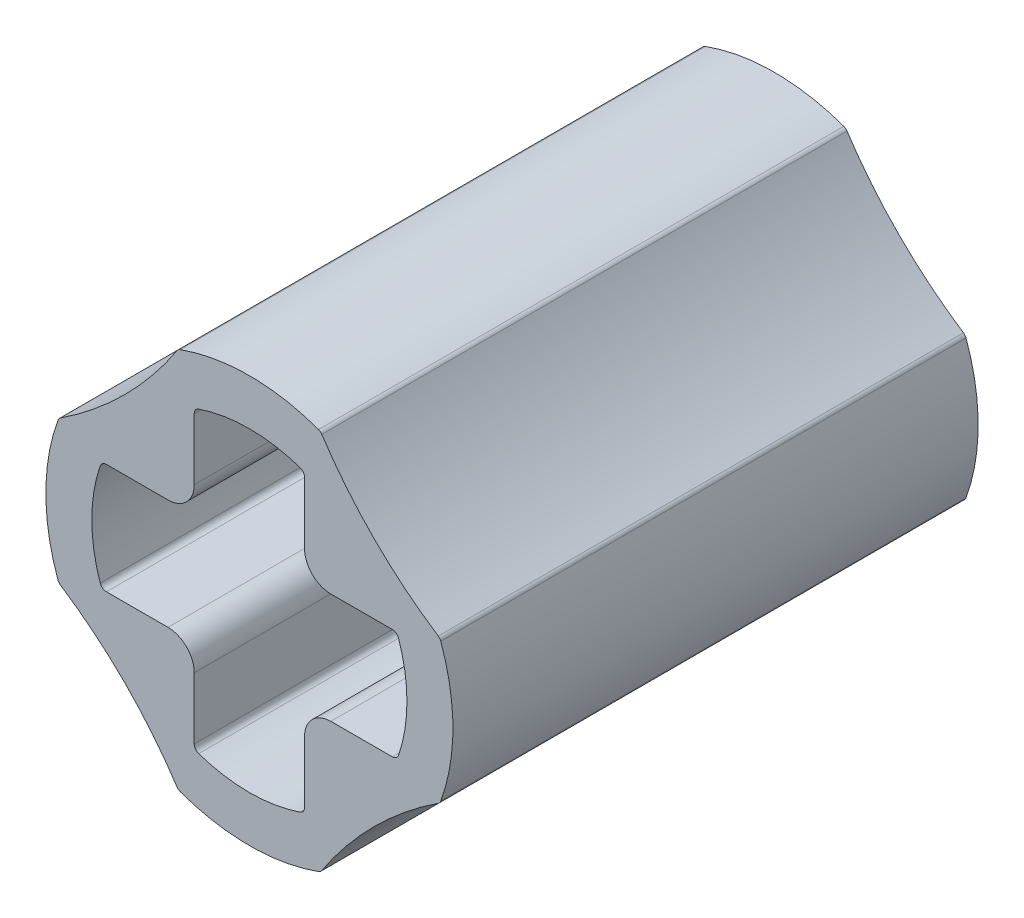
SolidWorks part; units mm, degrees
ref_plane "Front Plane" through (0, 0, 0) normal (0, 0, 1) x (1, 0, 0)
ref_plane "Top Plane" through (0, 0, 0) normal (0, 1, 0) x (1, 0, 0)
ref_plane "Right Plane" through (0, 0, 0) normal (1, 0, 0) x (0, 0, -1)
sketch "Sketch1" plane through (0, 0, 0) normal (0, 0, 1) x (1, 0, 0)
  line L0 (-1.085, -1.085) -> (-1.085, -2.9039)
  line L2 (-1.085, 2.9039) -> (-1.085, 1.085)
  line L4 (1.085, 2.9039) -> (1.085, 1.085)
  line L5 (-1.085, 2.9039) -> (1.085, -2.9039) construction
  line L6 (-1.085, -2.9039) -> (1.085, 2.9039) construction
  line L7 (-2.9039, 1.085) -> (-1.085, 1.085)
  line L9 (-2.9039, -1.085) -> (-1.085, -1.085)
  line L11 (-2.9039, 1.085) -> (2.9039, -1.085) construction
  line L12 (-2.9039, -1.085) -> (2.9039, 1.085) construction
  line L13 (1.085, -1.085) -> (1.085, -2.9039)
  line L14 (1.085, -1.085) -> (2.9039, -1.085)
  line L15 (1.085, 1.085) -> (2.9039, 1.085)
  arc A0 (1.085, 2.9039) -> (-1.085, 2.9039) centre (0, 0) ccw
  arc A1 (-2.9039, 1.085) -> (-2.9039, -1.085) centre (0, 0) ccw
  arc A2 (-1.085, -2.9039) -> (1.085, -2.9039) centre (0, 0) ccw
  arc A3 (2.9039, -1.085) -> (2.9039, 1.085) centre (0, 0) ccw
  dimension "D1" = 6.2
  dimension "D2" = 2.17
  dimension "D3" = 2.17
extrude "Boss-Extrude1" add sketch "Sketch1" along normal blind 8
sketch "Sketch2" plane through (0, 0, 0) normal (0, 0, 1) x (1, 0, 0)
  line L0 (0.84, -0.84) -> (2.2482, -0.84)
  line L2 (-0.84, 2.2482) -> (-0.84, 0.84)
  line L4 (0.84, 2.2482) -> (0.84, 0.84)
  line L5 (-0.84, 2.2482) -> (0.84, -2.2482) construction
  line L6 (-0.84, -2.2482) -> (0.84, 2.2482) construction
  line L7 (-2.2482, 0.84) -> (-0.84, 0.84)
  line L9 (-2.2482, -0.84) -> (-0.84, -0.84)
  line L11 (-2.2482, 0.84) -> (2.2482, -0.84) construction
  line L12 (-2.2482, -0.84) -> (2.2482, 0.84) construction
  line L13 (-0.84, -0.84) -> (-0.84, -2.2482)
  line L14 (0.84, 0.84) -> (2.2482, 0.84)
  line L15 (0.84, -0.84) -> (0.84, -2.2482)
  arc A0 (-2.2482, 0.84) -> (-2.2482, -0.84) centre (0, 0) ccw
  arc A1 (0.84, 2.2482) -> (-0.84, 2.2482) centre (0, 0) ccw
  arc A2 (2.2482, -0.84) -> (2.2482, 0.84) centre (0, 0) ccw
  arc A3 (-0.84, -2.2482) -> (0.84, -2.2482) centre (0, 0) ccw
  dimension "D1" = 4.8
  dimension "D2" = 1.68
  dimension "D3" = 1.68
extrude "Cut-Extrude1" cut sketch "Sketch2" along normal blind 8
fillet "Fillet1" radius 0.4 1 edges at (-0.84, 0.84, 4)
fillet "Fillet2" radius 0.4 1 edges at (0.84, 0.84, 4)
fillet "Fillet3" radius 0.4 1 edges at (0.84, -0.84, 4)
fillet "Fillet4" radius 0.4 1 edges at (-0.84, -0.84, 4)
fillet "Fillet5" radius 6.2 1 edges at (-1.085, 1.085, 4)
fillet "Fillet6" radius 6.2 1 edges at (-1.085, -1.085, 4)
fillet "Fillet7" radius 6.2 1 edges at (1.085, -1.085, 4)
fillet "Fillet8" radius 6.2 1 edges at (1.085, 1.085, 4)
fillet "Fillet9" radius 0.1 1 edges at (0.84, 2.2482, 4)
fillet "Fillet10" radius 0.1 1 edges at (1.085, 2.9039, 4)
fillet "Fillet11" radius 0.1 1 edges at (-1.085, 2.9039, 4)
fillet "Fillet12" radius 0.1 1 edges at (-2.9039, 1.085, 4)
fillet "Fillet13" radius 0.1 1 edges at (-2.9039, -1.085, 4)
fillet "Fillet14" radius 0.1 1 edges at (-1.085, -2.9039, 4)
fillet "Fillet15" radius 0.1 1 edges at (1.085, -2.9039, 4)
fillet "Fillet16" radius 0.1 1 edges at (2.9039, -1.085, 4)
fillet "Fillet17" radius 0.1 1 edges at (2.9039, 1.085, 4)
fillet "Fillet18" radius 0.1 1 edges at (0.84, -2.2482, 4)
fillet "Fillet19" radius 0.1 1 edges at (-0.84, -2.2482, 4)
fillet "Fillet20" radius 0.1 1 edges at (-2.2482, 0.84, 4)
fillet "Fillet21" radius 0.1 1 edges at (-2.2482, -0.84, 4)
fillet "Fillet22" radius 0.1 1 edges at (-0.84, 2.2482, 4)
fillet "Fillet23" radius 0.1 1 edges at (2.2482, -0.84, 4)
fillet "Fillet24" radius 0.1 1 edges at (2.2482, 0.84, 4)
